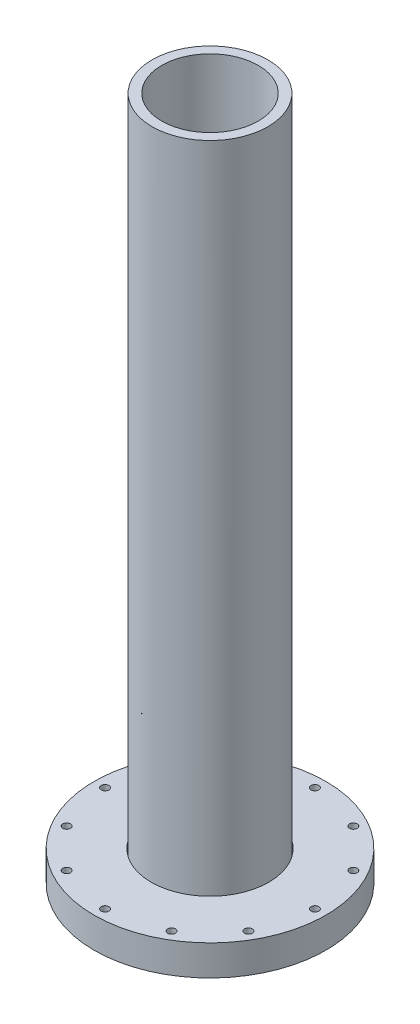
SolidWorks part; units mm, degrees
material "AISI 304"
ref_plane "Front Plane" through (0, 0, 0) normal (0, 0, 1) x (1, 0, 0)
ref_plane "Top Plane" through (0, 0, 0) normal (0, 1, 0) x (1, 0, 0)
ref_plane "Right Plane" through (0, 0, 0) normal (1, 0, 0) x (0, 0, -1)
sketch "Sketch1" plane through (0, 0, 0) normal (0, 1, 0) x (1, 0, 0)
  circle A0 centre (0, 0) radius 31.75
  circle A1 centre (0, 0) radius 38.1
  dimension "D1" = 63.5
  dimension "D2" = 76.2
extrude "Boss-Extrude1" add sketch "Sketch1" along normal blind 450
sketch "Sketch2" plane through (0, 0, 0) normal (0, 1, 0) x (1, 0, 0)
  circle A0 centre (0, 0) radius 76.2
  circle A3 centre (0, 0) radius 76.2 construction
  circle A4 centre (0, 0) radius 38.6715
  circle A5 centre (0, 0) radius 38.1 construction
  dimension "D1" = 0.5715
extrude "Boss-Extrude2" add sketch "Sketch2" along normal blind 20 separate body
hole_wizard "#10 Clearance Hole1" positions "Sketch4" profile "Sketch5" hole size "#10" standard "ANSI Inch" end condition through all
sketch "Sketch4" plane through (0, 0, 0) normal (0, -1, 0) x (-1, 0, 0)
  point P0 (-69, 0)
  point P12 (-59.7558, 34.5)
  point P13 (-34.5, 59.7558)
  point P14 (0, 69)
  point P15 (34.5, 59.7558)
  point P16 (59.7558, 34.5)
  point P17 (69, 0)
  point P18 (59.7558, -34.5)
  point P19 (34.5, -59.7558)
  point P20 (0, -69)
  point P21 (-34.5, -59.7558)
  point P22 (-59.7558, -34.5)
  dimension "D1" = 69
  dimension "D2" = 12
sketch "Sketch5" plane through (69, 0, 0) normal (1, 0, 0) x (0, 0, -1)
  line L0 (0, 0) -> (0, 450)
  line L1 (0, 450) -> (2.5527, 450)
  line L2 (2.5527, 450) -> (2.5527, 0)
  line L5 (2.5527, 0) -> (0, 0)
  line L11 (0, -6.35) -> (0, 107.95) construction
  dimension "Thru Hole Dia." = 5.1054
  dimension "Thru Hole Depth" = 450
ref_axis "Axis1" through (0, 472.5, 0) along (0, -1, 0)
sketch "Sketch6" plane through (0, 0, 0) normal (0, -1, 0) x (1, 0, 0)
  circle A0 centre (0, 0) radius 55.14 construction
  circle A1 centre (0, 0) radius 55.14
extrude "Cut-Extrude1" cut sketch "Sketch6" against normal blind 2
equation "\"D1@Sketch2\"=0.045/2"
